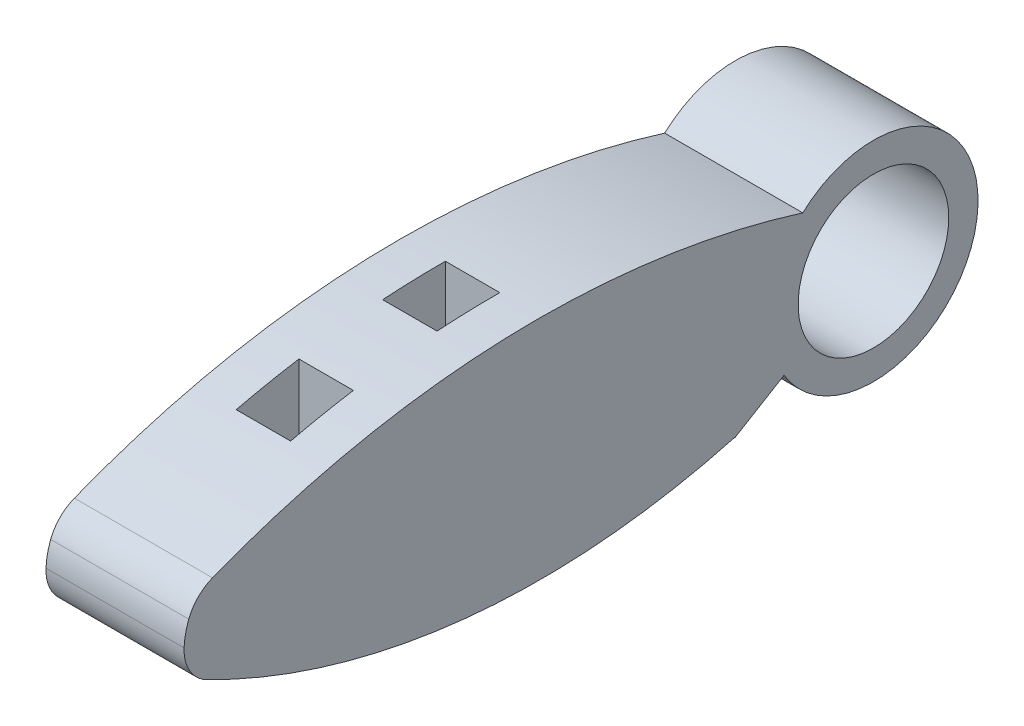
SolidWorks part; units mm, degrees
ref_plane "Front Plane" through (0, 0, 0) normal (0, 0, 1) x (1, 0, 0)
ref_plane "Top Plane" through (0, 0, 0) normal (0, 1, 0) x (1, 0, 0)
ref_plane "Right Plane" through (0, 0, 0) normal (1, 0, 0) x (0, 0, -1)
sketch "Sketch1" plane through (0, 0, 0) normal (1, 0, 0) x (0, 0, -1)
  circle A0 centre (0, 0) radius 6.35
  dimension "D1" = 12.7
extrude "Boss-Extrude1" add sketch "Sketch1" along normal blind 8.382
sketch "Sketch6" plane through (0, 0, 0) normal (0, 0, 1) x (1, 0, 0)
  line L1 (0, 5.08) -> (8.382, 5.08)
  line L2 (0, 5.08) -> (0, -5.08)
  line L3 (0, -5.08) -> (8.382, -5.08)
  line L4 (8.382, 5.08) -> (8.382, -5.08)
  line L5 (0, 6.35) -> (0, -6.35) construction
  line L6 (8.382, -6.35) -> (8.382, 6.35) construction
  dimension "D1" = 0
  dimension "D2" = 0
  dimension "D3" = 5.08
  dimension "D4" = 10.16
extrude "Boss-Extrude2" add sketch "Sketch6" along normal blind 31.75
sketch "Sketch5" plane through (0, 0, 0) normal (0, 1, 0) x (1, 0, 0)
  line L1 (8.382, 12.7) -> (5.842, 12.7)
  line L2 (8.382, 12.7) -> (8.382, 0)
  line L3 (8.382, 0) -> (5.842, 0)
  line L4 (5.842, 12.7) -> (5.842, 0)
  line L5 (8.382, -3.81) -> (8.382, 6.35) construction
  dimension "D1" = 12.7
  dimension "D2" = 0
  dimension "D3" = 2.54
  dimension "D4" = 0
sketch "Sketch8" plane through (8.382, 0, 0) normal (1, 0, 0) x (0, 0, -1)
  arc A2 (-4.2921, 4.6797) -> (-5.2242, -3.6098) centre (0, 0) ccw
  arc A4 (-7.5987, -4.8272) -> (-41.526, -1.2198) centre (-20.1957, 38.0452) cw
  arc A5 (-4.2921, 4.6797) -> (-40.9154, 3.0883) centre (-20.4005, -46.8189) ccw
  arc A6 (-40.9154, 3.0883) -> (-41.526, -1.2198) centre (-37.5759, 0.4177) ccw
  arc A7 (-5.2242, -3.6098) -> (-7.5987, -4.8272) centre (-16.6163, 15.6866) cw
  arc A8 (-3.81, -5.08) -> (-3.81, 5.08) centre (0, 0) ccw construction
  arc A9 (-3.81, -5.08) -> (-3.81, 5.08) centre (0, 0) ccw construction
sketch "Sketch9" plane through (0, 0, 0) normal (-1, 0, 0) x (0, 0, 1)
  line L0 (31.75, -5.08) -> (3.81, -5.08) construction
  line L1 (31.75, 5.08) -> (11.4084, 5.08)
  line L2 (31.75, 5.08) -> (31.75, -5.08)
  line L3 (31.75, -5.08) -> (11.4084, -5.08)
  line L4 (11.4084, 0.9555) -> (11.4084, -5.08)
  line L5 (11.4084, 5.08) -> (3.81, 5.08)
  line L6 (6.0928, 0.9555) -> (11.4084, 0.9555)
  arc A0 (3.81, 5.08) -> (6.0928, 0.9555) centre (-0.3346, 0.0921) cw
extrude "Cut-Extrude4" cut sketch "Sketch9" against normal blind 37.592
extrude "Boss-Extrude3" add sketch "Sketch8" against normal up to surface (8.382 mm away) up to face at (0, -0.5908, 5.3515)
sketch "Sketch11" plane through (8.382, 0, 0) normal (1, 0, 0) x (0, 0, -1)
  circle A0 centre (0, 0) radius 6.35
extrude "Boss-Extrude4" add sketch "Sketch11" along normal up to surface (-8.382 mm away) up to face at (0, 0.4831, 13.3581)
fillet "Fillet1" radius 2.54 2 edges at (4.191, -1.2198, 41.526) (4.191, 3.0883, 40.9154)
sketch "Sketch12" plane through (0, 0, 0) normal (-1, 0, 0) x (0, 0, 1)
  line L0 (5.3113, -3.4802) -> (6.4759, -5.08)
  line L1 (6.4759, -5.08) -> (3.81, -5.08)
  line L2 (8.4936, -5.08) -> (3.81, -5.08) construction
  arc A0 (3.81, -5.08) -> (5.3113, -3.4802) centre (0, 0) ccw
  arc A1 (4.2921, 4.6797) -> (3.81, -5.08) centre (0, 0) ccw construction
extrude "Cut-Extrude5" cut sketch "Sketch12" against normal blind 12.192
sketch "Sketch13" plane through (0, -5.08, 0) normal (0, -1, 0) x (1, 0, 0)
  line L0 (0, 40.4627) -> (0, 8.4936) construction
  line L1 (2.54, 29.0327) -> (5.842, 29.0327)
  line L2 (2.54, 29.0327) -> (2.54, 32.8427)
  line L3 (2.54, 32.8427) -> (5.842, 32.8427)
  line L4 (5.842, 29.0327) -> (5.842, 32.8427)
  line L5 (2.54, 20.1427) -> (5.842, 20.1427)
  line L6 (2.54, 20.1427) -> (2.54, 23.9527)
  line L7 (2.54, 23.9527) -> (5.842, 23.9527)
  line L8 (5.842, 20.1427) -> (5.842, 23.9527)
  line L9 (8.382, 8.4936) -> (8.382, 40.4627) construction
  line L10 (8.382, 40.4627) -> (0, 40.4627) construction
  point P14 (4.191, 23.9527)
  dimension "D1" = 2.54
  dimension "D2" = 2.54
  dimension "D3" = 7.62
  dimension "D4" = 3.81
  dimension "D5" = 5.08
  dimension "D6" = 3.81
extrude "Cut-Extrude6" cut sketch "Sketch13" against normal through all and the other way blind 2.54
sketch "Sketch14" plane through (0, -5.08, 0) normal (0, -1, 0) x (1, 0, 0)
  line L1 (3.048, -10.7011) -> (5.334, -10.7011)
  line L2 (3.048, -10.7011) -> (3.048, 29.0327)
  line L3 (3.048, 29.0327) -> (5.334, 29.0327)
  line L4 (5.334, -10.7011) -> (5.334, 29.0327)
  line L6 (0, 8.4936) -> (0, 6.4759) construction
  line L7 (8.382, 8.4936) -> (8.382, 6.4759) construction
  line L8 (5.842, 29.0327) -> (2.54, 29.0327) construction
  dimension "D1" = 3.048
  dimension "D2" = 3.048
extrude "Cut-Extrude7" cut sketch "Sketch14" along normal blind 5.842 and the other way blind 2.032
sketch "Sketch15" plane through (5.334, 0, 0) normal (-1, 0, 0) x (0, 0, 1)
  line L0 (20.1427, -3.048) -> (5.3113, -4.064)
  line L1 (5.3113, -3.4802) -> (5.3113, -3.048) construction
  line L2 (-5.5707, -3.048) -> (20.1427, -3.048) construction
  line L7 (5.3113, -3.4802) -> (6.4759, -5.08)
  line L8 (6.4759, -5.08) -> (8.4936, -5.08)
  line L9 (20.1427, -6.6395) -> (20.1427, -3.048)
  line L10 (20.1427, -3.048) -> (-5.5707, -3.048)
  line L14 (20.1427, -3.048) -> (-4.8087, -3.048)
  arc A0 (5.3113, -4.064) -> (-4.8087, -3.048) centre (0.7827, 1.7368) cw
  arc A1 (-5.5707, -3.048) -> (5.3113, -3.4802) centre (0, 0) ccw construction
  arc A4 (8.4936, -5.08) -> (20.1427, -6.6395) centre (20.1957, 38.0452) ccw
  arc A5 (-5.5707, -3.048) -> (5.3113, -3.4802) centre (0, 0) ccw
  dimension "D1" = 1.905
  dimension "D2" = 1.016
  dimension "D3" = 0.762
  dimension "D4" = 0
extrude "Boss-Extrude5" add sketch "Sketch15" along normal blind 2.286
sketch "Sketch17" plane through (0, 0, 0) normal (0, 0, 1) x (1, 0, 0)
  line L0 (14.3096, 0) -> (-8.4266, 0) construction
sketch "Sketch16" plane through (0, -3.048, 0) normal (0, -1, 0) x (1, 0, 0)
  line L4 (14.2945, 11.7013) -> (-8.7816, 11.7013) construction
  line L5 (3.048, -4.8087) -> (5.334, -4.8087) construction
  line L12 (5.334, -4.8087) -> (3.048, -4.8087)
  line L13 (3.048, -4.8087) -> (3.048, -6.0787)
  line L14 (3.048, -6.0787) -> (5.334, -6.7297)
  line L15 (5.334, -6.7297) -> (5.334, -4.8087)
  dimension "D1" = 1.27
  dimension "D2" = 0
  dimension "D3" = 16.51
revolve "Cut-Revolve1" [suppressed] cut sketch "Sketch16" angle 15 about L4 reverse direction yes
fillet "Fillet2" [suppressed] radius 5.842
sketch "Sketch18" plane through (0, 0, 23.9527) normal (0, 0, -1) x (-1, 0, 0)
  line L0 (-5.842, -6.4813) -> (-5.842, 7.0232) construction
  line L1 (-5.842, 5.3658) -> (-2.54, 5.3658)
  line L2 (-5.842, 5.3658) -> (-5.842, 9.5632)
  line L3 (-5.842, 9.5632) -> (-2.54, 9.5632)
  line L4 (-2.54, 5.3658) -> (-2.54, 9.5632)
  line L5 (-5.842, 7.0232) -> (-2.54, 7.0232) construction
  dimension "D1" = 2.54
extrude "Boss-Extrude6" [suppressed] add sketch "Sketch18" against normal up to surface (5.08 mm away)
fillet "Fillet3" [suppressed] type full round
sketch "Sketch19" plane through (8.382, 0, 0) normal (1, 0, 0) x (0, 0, -1)
  circle A0 centre (0, 0) radius 6.35
  circle A1 centre (0, 0) radius 4.572
  dimension "D1" = 1.778
extrude "Cut-Extrude8" cut sketch "Sketch19" against normal blind 20.32 contours A1 region at (8.382, 0, 0)
chamfer "Chamfer1" distance 2.54 angle 23 2 edges at (1.524, -5.08, 6.4759) (6.858, -5.08, 6.4759) first distance on face at (1.8288, -4.2314, 5.8581) first distance on face at (6.5532, -4.2314, 5.8581)
